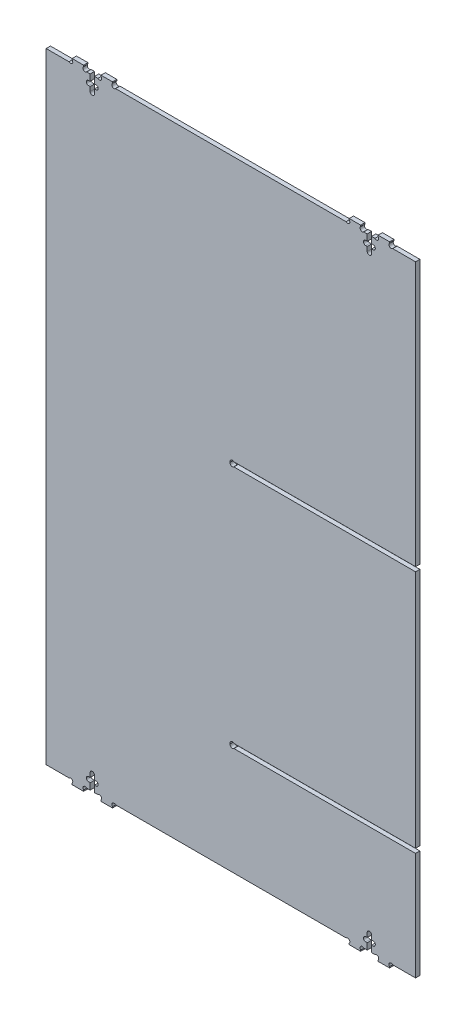
SolidWorks part; units mm, degrees
ref_plane "Спереди" through (0, 0, 0) normal (0, 0, 1) x (1, 0, 0)
ref_plane "Сверху" through (0, 0, 0) normal (0, 1, 0) x (1, 0, 0)
ref_plane "Справа" through (0, 0, 0) normal (1, 0, 0) x (0, 0, -1)
sketch "Эскиз1" plane through (0, 0, 0) normal (0, 0, 1) x (1, 0, 0)
  line L1 (171.206, 664.8747) -> (-352.794, 664.8747)
  line L2 (171.206, 664.8747) -> (171.206, -200.7253)
  line L3 (171.206, -200.7253) -> (-352.794, -200.7253)
  line L4 (-352.794, 664.8747) -> (-352.794, -200.7253)
  dimension "X001" = 352.794
  dimension "X002" = 171.206
  dimension "Y001" = 200.7253
  dimension "Y002" = 664.8747
extrude "Бобышка-Вытянуть1" add sketch "Эскиз1" against normal blind 6
sketch "Стыки_эскиз_добавленных_шипов" plane through (0, 0, 0) normal (0, 0, 1) x (1, 0, 0)
  line L0 (-254.794, -206.7253) -> (-254.794, -200.7153)
  line L1 (-254.794, -200.7153) -> (-270.794, -200.7153)
  line L2 (-270.794, -200.7153) -> (-270.794, -206.7253)
  line L3 (-270.794, -206.7253) -> (-254.794, -206.7253)
  line L4 (-294.794, -200.7153) -> (-310.794, -200.7153)
  line L5 (-310.794, -200.7153) -> (-310.794, -206.7253)
  line L6 (-310.794, -206.7253) -> (-294.794, -206.7253)
  line L7 (-294.794, -206.7253) -> (-294.794, -200.7153)
  line L8 (129.206, -200.7153) -> (113.206, -200.7153)
  line L9 (113.206, -200.7153) -> (113.206, -206.7253)
  line L10 (113.206, -206.7253) -> (129.206, -206.7253)
  line L11 (129.206, -206.7253) -> (129.206, -200.7153)
  line L12 (73.206, -206.7253) -> (89.206, -206.7253)
  line L13 (89.206, -206.7253) -> (89.206, -200.7153)
  line L14 (89.206, -200.7153) -> (73.206, -200.7153)
  line L15 (73.206, -200.7153) -> (73.206, -206.7253)
  dimension "X001" = 310.794
  dimension "X002" = 294.794
  dimension "X003" = 270.794
  dimension "X004" = 254.794
  dimension "X005" = 73.206
  dimension "X006" = 89.206
  dimension "X007" = 113.206
  dimension "X008" = 129.206
  dimension "Y001" = 206.7253
  dimension "Y002" = 200.7153
extrude "Стыки_добавленные_шипы_6мм" add sketch "Стыки_эскиз_добавленных_шипов" against normal blind 6
sketch "Стыки_эскиз_пазов_и_стяжек_М5" plane through (0, 0, 0) normal (0, 0, 1) x (1, 0, 0)
  line L0 (-280.044, -190.8753) -> (-278.644, -190.8753)
  line L1 (-278.644, -190.8753) -> (-278.644, -186.5753)
  line L2 (-278.644, -186.5753) -> (-280.044, -186.5753)
  line L3 (-280.044, -186.5753) -> (-280.044, -179.7253)
  line L4 (-280.044, -179.7253) -> (-285.544, -179.7253)
  line L5 (-285.544, -179.7253) -> (-285.544, -186.5753)
  line L6 (-285.544, -186.5753) -> (-286.944, -186.5753)
  line L7 (-286.944, -186.5753) -> (-286.944, -190.8753)
  line L8 (-286.944, -190.8753) -> (-285.544, -190.8753)
  line L9 (-285.544, -190.8753) -> (-285.544, -206.8253)
  line L10 (-285.544, -206.8253) -> (-280.044, -206.8253)
  line L11 (-280.044, -206.8253) -> (-280.044, -190.8753)
  line L12 (-352.894, 664.8747) -> (-352.894, 658.8747)
  line L13 (-352.894, 658.8747) -> (-352.794, 658.8747)
  line L14 (-352.794, 658.8747) -> (-352.794, -200.7253)
  line L15 (-352.794, -200.7253) -> (-346.794, -200.7253)
  line L16 (-346.794, -200.7253) -> (-346.794, 658.8747)
  line L17 (-346.794, 658.8747) -> (-310.794, 658.8747)
  line L18 (-310.794, 658.8747) -> (-310.794, 664.8747)
  line L19 (-310.794, 664.8747) -> (-352.894, 664.8747)
  line L20 (-90.869, -51.2003) -> (165.206, -51.2003)
  line L21 (165.206, -51.2003) -> (165.206, -200.7253)
  line L22 (165.206, -200.7253) -> (171.206, -200.7253)
  line L23 (171.206, -200.7253) -> (171.206, -51.2003)
  line L24 (171.206, -51.2003) -> (171.306, -51.2003)
  line L25 (171.306, -51.2003) -> (171.306, -45.0503)
  line L26 (171.306, -45.0503) -> (171.206, -45.0503)
  line L27 (171.206, -45.0503) -> (171.206, 286.7997)
  line L28 (171.206, 286.7997) -> (171.306, 286.7997)
  line L29 (171.306, 286.7997) -> (171.306, 292.9497)
  line L30 (171.306, 292.9497) -> (171.206, 292.9497)
  line L31 (171.206, 292.9497) -> (171.206, 658.8747)
  line L32 (171.206, 658.8747) -> (171.306, 658.8747)
  line L33 (171.306, 658.8747) -> (171.306, 664.8747)
  line L34 (171.306, 664.8747) -> (129.206, 664.8747)
  line L35 (129.206, 664.8747) -> (129.206, 658.8747)
  line L36 (129.206, 658.8747) -> (165.206, 658.8747)
  line L37 (165.206, 658.8747) -> (165.206, 292.9497)
  line L38 (165.206, 292.9497) -> (-90.869, 292.9497)
  line L39 (-90.869, 292.9497) -> (-90.869, 286.7997)
  line L40 (-90.869, 286.7997) -> (165.206, 286.7997)
  line L41 (165.206, 286.7997) -> (165.206, -45.0503)
  line L42 (165.206, -45.0503) -> (-90.869, -45.0503)
  line L43 (-90.869, -45.0503) -> (-90.869, -51.2003)
  line L44 (98.456, 658.8747) -> (98.456, 649.0247)
  line L45 (98.456, 649.0247) -> (97.056, 649.0247)
  line L46 (97.056, 649.0247) -> (97.056, 644.7247)
  line L47 (97.056, 644.7247) -> (98.456, 644.7247)
  line L48 (98.456, 644.7247) -> (98.456, 637.8747)
  line L49 (98.456, 637.8747) -> (103.956, 637.8747)
  line L50 (103.956, 637.8747) -> (103.956, 644.7247)
  line L51 (103.956, 644.7247) -> (105.356, 644.7247)
  line L52 (105.356, 644.7247) -> (105.356, 649.0247)
  line L53 (105.356, 649.0247) -> (103.956, 649.0247)
  line L54 (103.956, 649.0247) -> (103.956, 658.8747)
  line L55 (103.956, 658.8747) -> (113.206, 658.8747)
  line L56 (113.206, 658.8747) -> (113.206, 664.8747)
  line L57 (113.206, 664.8747) -> (103.956, 664.8747)
  line L58 (103.956, 664.8747) -> (103.956, 664.9747)
  line L59 (103.956, 664.9747) -> (98.456, 664.9747)
  line L60 (98.456, 664.9747) -> (98.456, 664.8747)
  line L61 (98.456, 664.8747) -> (89.206, 664.8747)
  line L62 (89.206, 664.8747) -> (89.206, 658.8747)
  line L63 (89.206, 658.8747) -> (98.456, 658.8747)
  line L64 (-285.544, 658.8747) -> (-285.544, 649.0247)
  line L65 (-285.544, 649.0247) -> (-286.944, 649.0247)
  line L66 (-286.944, 649.0247) -> (-286.944, 644.7247)
  line L67 (-286.944, 644.7247) -> (-285.544, 644.7247)
  line L68 (-285.544, 644.7247) -> (-285.544, 637.8747)
  line L69 (-285.544, 637.8747) -> (-280.044, 637.8747)
  line L70 (-280.044, 637.8747) -> (-280.044, 644.7247)
  line L71 (-280.044, 644.7247) -> (-278.644, 644.7247)
  line L72 (-278.644, 644.7247) -> (-278.644, 649.0247)
  line L73 (-278.644, 649.0247) -> (-280.044, 649.0247)
  line L74 (-280.044, 649.0247) -> (-280.044, 658.8747)
  line L75 (-280.044, 658.8747) -> (-270.794, 658.8747)
  line L76 (-270.794, 658.8747) -> (-270.794, 664.8747)
  line L77 (-270.794, 664.8747) -> (-280.044, 664.8747)
  line L78 (-280.044, 664.8747) -> (-280.044, 664.9747)
  line L79 (-280.044, 664.9747) -> (-285.544, 664.9747)
  line L80 (-285.544, 664.9747) -> (-285.544, 664.8747)
  line L81 (-285.544, 664.8747) -> (-294.794, 664.8747)
  line L82 (-294.794, 664.8747) -> (-294.794, 658.8747)
  line L83 (-294.794, 658.8747) -> (-285.544, 658.8747)
  line L84 (103.956, -206.8253) -> (103.956, -190.8753)
  line L85 (103.956, -190.8753) -> (105.356, -190.8753)
  line L86 (105.356, -190.8753) -> (105.356, -186.5753)
  line L87 (105.356, -186.5753) -> (103.956, -186.5753)
  line L88 (103.956, -186.5753) -> (103.956, -179.7253)
  line L89 (103.956, -179.7253) -> (98.456, -179.7253)
  line L90 (98.456, -179.7253) -> (98.456, -186.5753)
  line L91 (98.456, -186.5753) -> (97.056, -186.5753)
  line L92 (97.056, -186.5753) -> (97.056, -190.8753)
  line L93 (97.056, -190.8753) -> (98.456, -190.8753)
  line L94 (98.456, -190.8753) -> (98.456, -206.8253)
  line L95 (98.456, -206.8253) -> (103.956, -206.8253)
  line L96 (73.206, 658.8747) -> (73.206, 664.8747)
  line L97 (73.206, 664.8747) -> (-254.794, 664.8747)
  line L98 (-254.794, 664.8747) -> (-254.794, 658.8747)
  line L99 (-254.794, 658.8747) -> (73.206, 658.8747)
  dimension "X001" = 352.894
  dimension "X002" = 352.794
  dimension "X003" = 346.794
  dimension "X004" = 310.794
  dimension "X005" = 294.794
  dimension "X006" = 286.944
  dimension "X007" = 285.544
  dimension "X008" = 280.044
  dimension "X009" = 278.644
  dimension "X010" = 270.794
  dimension "X011" = 254.794
  dimension "X012" = 90.869
  dimension "X013" = 73.206
  dimension "X014" = 89.206
  dimension "X015" = 97.056
  dimension "X016" = 98.456
  dimension "X017" = 103.956
  dimension "X018" = 105.356
  dimension "X019" = 113.206
  dimension "X020" = 129.206
  dimension "X021" = 165.206
  dimension "X022" = 171.206
  dimension "X023" = 171.306
  dimension "Y001" = 206.8253
  dimension "Y002" = 200.7253
  dimension "Y003" = 190.8753
  dimension "Y004" = 186.5753
  dimension "Y005" = 179.7253
  dimension "Y006" = 51.2003
  dimension "Y007" = 45.0503
  dimension "Y008" = 286.7997
  dimension "Y009" = 292.9497
  dimension "Y010" = 637.8747
  dimension "Y011" = 644.7247
  dimension "Y012" = 649.0247
  dimension "Y013" = 658.8747
  dimension "Y014" = 664.8747
  dimension "Y015" = 664.9747
extrude "Стыки_шип_паз_стяжки_М5" cut sketch "Стыки_эскиз_пазов_и_стяжек_М5" against normal through all and the other way through all
sketch "ЧПУ_М6_01_Центр" plane through (0, 0, 0) normal (0, 0, 1) x (1, 0, 0)
  line L0 (-286.944, 644.7247) -> (-286.944, 649.0247) construction
  line L1 (-278.644, 644.7247) -> (-280.044, 644.7247) construction
  point P0 (-282.794, 646.8747)
  dimension "От_кромки_по_X" = 4.15
  dimension "От_кромки_по_Y" = 2.15
sketch "ЧПУ_М6_01_Канал_эскиз" plane through (0, 0, 0) normal (0, 0, 1) x (1, 0, 0)
  line L0 (-285.794, 637.7747) -> (-279.794, 637.7747)
  line L1 (-279.794, 637.7747) -> (-279.794, 658.9747)
  line L2 (-279.794, 658.9747) -> (-285.794, 658.9747)
  line L3 (-285.794, 658.9747) -> (-285.794, 637.7747)
  line L4 (-285.794, 637.7747) -> (-279.794, 658.9747) construction
  point P4 (-282.794, 648.3747)
  dimension "Ширина" = 6
  dimension "Глубина" = 21.2
  dimension "Положение_ОтКромки" = 1.5
extrude "ЧПУ_М6_01_Канал" cut sketch "ЧПУ_М6_01_Канал_эскиз" against normal through all and the other way through all
sketch "ЧПУ_М6_01_Гайка_эскиз" plane through (0, 0, 0) normal (0, 0, 1) x (1, 0, 0)
  line L0 (-287.944, 643.7747) -> (-277.644, 643.7747)
  line L1 (-277.644, 643.7747) -> (-277.644, 649.9747)
  line L2 (-277.644, 649.9747) -> (-287.944, 649.9747)
  line L3 (-287.944, 649.9747) -> (-287.944, 643.7747)
  line L4 (-287.944, 643.7747) -> (-277.644, 649.9747) construction
  point P4 (-282.794, 646.8747)
  dimension "Ширина" = 10.3
  dimension "Глубина" = 6.2
extrude "ЧПУ_М6_01_Гайка" cut sketch "ЧПУ_М6_01_Гайка_эскиз" against normal through all and the other way through all
sketch "ЧПУ_М6_01_Т_эскиз_1" plane through (0, 0, 0) normal (0, 0, 1) x (1, 0, 0)
  circle A0 centre (-277.644, 646.9247) radius 3.05
  circle A1 centre (-287.944, 646.9247) radius 3.05
  dimension "Диаметр1" = 6.1
  dimension "Диаметр2" = 6.1
  dimension "Центр1_ПоОси" = 5.15
  dimension "Центр1_ОтКромки" = 0.05
  dimension "Центр2_ПоОси" = 5.15
  dimension "Центр2_ОтКромки" = 0.05
extrude "ЧПУ_М6_01_Т_разгрузка_1" cut sketch "ЧПУ_М6_01_Т_эскиз_1" against normal through all and the other way through all
sketch "ЧПУ_М6_01_Т_эскиз_-1" plane through (0, 0, 0) normal (0, 0, 1) x (1, 0, 0)
  circle A0 centre (-277.644, 646.8247) radius 3.05
  circle A1 centre (-287.944, 646.8247) radius 3.05
  dimension "Диаметр1" = 6.1
  dimension "Диаметр2" = 6.1
  dimension "Центр1_ПоОси" = 5.15
  dimension "Центр1_ОтКромки" = 0.05
  dimension "Центр2_ПоОси" = 5.15
  dimension "Центр2_ОтКромки" = 0.05
extrude "ЧПУ_М6_01_Т_разгрузка_-1" cut sketch "ЧПУ_М6_01_Т_эскиз_-1" against normal through all and the other way through all
sketch "ЧПУ_М6_01_Конец_эскиз" plane through (0, 0, 0) normal (0, 0, 1) x (1, 0, 0)
  circle A0 centre (-282.794, 637.7747) radius 3
  dimension "Центр1_ОтКромки" = 9.1
extrude "ЧПУ_М6_01_Конец" cut sketch "ЧПУ_М6_01_Конец_эскиз" against normal through all and the other way through all
sketch "ЧПУ_М6_02_Центр" plane through (0, 0, 0) normal (0, 0, 1) x (1, 0, 0)
  line L0 (97.056, 644.7247) -> (97.056, 649.0247) construction
  line L1 (105.356, 644.7247) -> (103.956, 644.7247) construction
  point P0 (101.206, 646.8747)
  dimension "От_кромки_по_X" = 4.15
  dimension "От_кромки_по_Y" = 2.15
sketch "ЧПУ_М6_02_Канал_эскиз" plane through (0, 0, 0) normal (0, 0, 1) x (1, 0, 0)
  line L0 (98.206, 637.7747) -> (104.206, 637.7747)
  line L1 (104.206, 637.7747) -> (104.206, 658.9747)
  line L2 (104.206, 658.9747) -> (98.206, 658.9747)
  line L3 (98.206, 658.9747) -> (98.206, 637.7747)
  line L4 (98.206, 637.7747) -> (104.206, 658.9747) construction
  point P4 (101.206, 648.3747)
  dimension "Ширина" = 6
  dimension "Глубина" = 21.2
  dimension "Положение_ОтКромки" = 1.5
extrude "ЧПУ_М6_02_Канал" cut sketch "ЧПУ_М6_02_Канал_эскиз" against normal through all and the other way through all
sketch "ЧПУ_М6_02_Гайка_эскиз" plane through (0, 0, 0) normal (0, 0, 1) x (1, 0, 0)
  line L0 (96.056, 643.7747) -> (106.356, 643.7747)
  line L1 (106.356, 643.7747) -> (106.356, 649.9747)
  line L2 (106.356, 649.9747) -> (96.056, 649.9747)
  line L3 (96.056, 649.9747) -> (96.056, 643.7747)
  line L4 (96.056, 643.7747) -> (106.356, 649.9747) construction
  point P4 (101.206, 646.8747)
  dimension "Ширина" = 10.3
  dimension "Глубина" = 6.2
extrude "ЧПУ_М6_02_Гайка" cut sketch "ЧПУ_М6_02_Гайка_эскиз" against normal through all and the other way through all
sketch "ЧПУ_М6_02_Т_эскиз_1" plane through (0, 0, 0) normal (0, 0, 1) x (1, 0, 0)
  circle A0 centre (106.356, 646.9247) radius 3.05
  circle A1 centre (96.056, 646.9247) radius 3.05
  dimension "Диаметр1" = 6.1
  dimension "Диаметр2" = 6.1
  dimension "Центр1_ПоОси" = 5.15
  dimension "Центр1_ОтКромки" = 0.05
  dimension "Центр2_ПоОси" = 5.15
  dimension "Центр2_ОтКромки" = 0.05
extrude "ЧПУ_М6_02_Т_разгрузка_1" cut sketch "ЧПУ_М6_02_Т_эскиз_1" against normal through all and the other way through all
sketch "ЧПУ_М6_02_Т_эскиз_-1" plane through (0, 0, 0) normal (0, 0, 1) x (1, 0, 0)
  circle A0 centre (106.356, 646.8247) radius 3.05
  circle A1 centre (96.056, 646.8247) radius 3.05
  dimension "Диаметр1" = 6.1
  dimension "Диаметр2" = 6.1
  dimension "Центр1_ПоОси" = 5.15
  dimension "Центр1_ОтКромки" = 0.05
  dimension "Центр2_ПоОси" = 5.15
  dimension "Центр2_ОтКромки" = 0.05
extrude "ЧПУ_М6_02_Т_разгрузка_-1" cut sketch "ЧПУ_М6_02_Т_эскиз_-1" against normal through all and the other way through all
sketch "ЧПУ_М6_02_Конец_эскиз" plane through (0, 0, 0) normal (0, 0, 1) x (1, 0, 0)
  circle A0 centre (101.206, 637.7747) radius 3
  dimension "Центр1_ОтКромки" = 9.1
extrude "ЧПУ_М6_02_Конец" cut sketch "ЧПУ_М6_02_Конец_эскиз" against normal through all and the other way through all
sketch "ЧПУ_М6_03_Центр" plane through (0, 0, 0) normal (0, 0, 1) x (1, 0, 0)
  line L0 (97.056, -190.8753) -> (97.056, -186.5753) construction
  line L1 (105.356, -190.8753) -> (103.956, -190.8753) construction
  point P0 (101.206, -188.7253)
  dimension "От_кромки_по_X" = 4.15
  dimension "От_кромки_по_Y" = 2.15
sketch "ЧПУ_М6_03_Канал_эскиз" plane through (0, 0, 0) normal (0, 0, 1) x (1, 0, 0)
  line L0 (98.206, -200.8253) -> (104.206, -200.8253)
  line L1 (104.206, -200.8253) -> (104.206, -179.6253)
  line L2 (104.206, -179.6253) -> (98.206, -179.6253)
  line L3 (98.206, -179.6253) -> (98.206, -200.8253)
  line L4 (98.206, -200.8253) -> (104.206, -179.6253) construction
  point P4 (101.206, -190.2253)
  dimension "Ширина" = 6
  dimension "Глубина" = 21.2
  dimension "Положение_ОтКромки" = 1.5
extrude "ЧПУ_М6_03_Канал" cut sketch "ЧПУ_М6_03_Канал_эскиз" against normal through all and the other way through all
sketch "ЧПУ_М6_03_Гайка_эскиз" plane through (0, 0, 0) normal (0, 0, 1) x (1, 0, 0)
  line L0 (96.056, -191.8253) -> (106.356, -191.8253)
  line L1 (106.356, -191.8253) -> (106.356, -185.6253)
  line L2 (106.356, -185.6253) -> (96.056, -185.6253)
  line L3 (96.056, -185.6253) -> (96.056, -191.8253)
  line L4 (96.056, -191.8253) -> (106.356, -185.6253) construction
  point P4 (101.206, -188.7253)
  dimension "Ширина" = 10.3
  dimension "Глубина" = 6.2
extrude "ЧПУ_М6_03_Гайка" cut sketch "ЧПУ_М6_03_Гайка_эскиз" against normal through all and the other way through all
sketch "ЧПУ_М6_03_Т_эскиз_1" plane through (0, 0, 0) normal (0, 0, 1) x (1, 0, 0)
  circle A0 centre (106.356, -188.6753) radius 3.05
  circle A1 centre (96.056, -188.6753) radius 3.05
  dimension "Диаметр1" = 6.1
  dimension "Диаметр2" = 6.1
  dimension "Центр1_ПоОси" = 5.15
  dimension "Центр1_ОтКромки" = 0.05
  dimension "Центр2_ПоОси" = 5.15
  dimension "Центр2_ОтКромки" = 0.05
extrude "ЧПУ_М6_03_Т_разгрузка_1" cut sketch "ЧПУ_М6_03_Т_эскиз_1" against normal through all and the other way through all
sketch "ЧПУ_М6_03_Т_эскиз_-1" plane through (0, 0, 0) normal (0, 0, 1) x (1, 0, 0)
  circle A0 centre (106.356, -188.7753) radius 3.05
  circle A1 centre (96.056, -188.7753) radius 3.05
  dimension "Диаметр1" = 6.1
  dimension "Диаметр2" = 6.1
  dimension "Центр1_ПоОси" = 5.15
  dimension "Центр1_ОтКромки" = 0.05
  dimension "Центр2_ПоОси" = 5.15
  dimension "Центр2_ОтКромки" = 0.05
extrude "ЧПУ_М6_03_Т_разгрузка_-1" cut sketch "ЧПУ_М6_03_Т_эскиз_-1" against normal through all and the other way through all
sketch "ЧПУ_М6_03_Конец_эскиз" plane through (0, 0, 0) normal (0, 0, 1) x (1, 0, 0)
  circle A0 centre (101.206, -179.6253) radius 3
  dimension "Центр1_ОтКромки" = 9.1
extrude "ЧПУ_М6_03_Конец" cut sketch "ЧПУ_М6_03_Конец_эскиз" against normal through all and the other way through all
sketch "ЧПУ_М6_04_Центр" plane through (0, 0, 0) normal (0, 0, 1) x (1, 0, 0)
  line L0 (-286.944, -190.8753) -> (-286.944, -186.5753) construction
  line L1 (-278.644, -190.8753) -> (-280.044, -190.8753) construction
  point P0 (-282.794, -188.7253)
  dimension "От_кромки_по_X" = 4.15
  dimension "От_кромки_по_Y" = 2.15
sketch "ЧПУ_М6_04_Канал_эскиз" plane through (0, 0, 0) normal (0, 0, 1) x (1, 0, 0)
  line L0 (-285.794, -200.8253) -> (-279.794, -200.8253)
  line L1 (-279.794, -200.8253) -> (-279.794, -179.6253)
  line L2 (-279.794, -179.6253) -> (-285.794, -179.6253)
  line L3 (-285.794, -179.6253) -> (-285.794, -200.8253)
  line L4 (-285.794, -200.8253) -> (-279.794, -179.6253) construction
  point P4 (-282.794, -190.2253)
  dimension "Ширина" = 6
  dimension "Глубина" = 21.2
  dimension "Положение_ОтКромки" = 1.5
extrude "ЧПУ_М6_04_Канал" cut sketch "ЧПУ_М6_04_Канал_эскиз" against normal through all and the other way through all
sketch "ЧПУ_М6_04_Гайка_эскиз" plane through (0, 0, 0) normal (0, 0, 1) x (1, 0, 0)
  line L0 (-287.944, -191.8253) -> (-277.644, -191.8253)
  line L1 (-277.644, -191.8253) -> (-277.644, -185.6253)
  line L2 (-277.644, -185.6253) -> (-287.944, -185.6253)
  line L3 (-287.944, -185.6253) -> (-287.944, -191.8253)
  line L4 (-287.944, -191.8253) -> (-277.644, -185.6253) construction
  point P4 (-282.794, -188.7253)
  dimension "Ширина" = 10.3
  dimension "Глубина" = 6.2
extrude "ЧПУ_М6_04_Гайка" cut sketch "ЧПУ_М6_04_Гайка_эскиз" against normal through all and the other way through all
sketch "ЧПУ_М6_04_Т_эскиз_1" plane through (0, 0, 0) normal (0, 0, 1) x (1, 0, 0)
  circle A0 centre (-277.644, -188.6753) radius 3.05
  circle A1 centre (-287.944, -188.6753) radius 3.05
  dimension "Диаметр1" = 6.1
  dimension "Диаметр2" = 6.1
  dimension "Центр1_ПоОси" = 5.15
  dimension "Центр1_ОтКромки" = 0.05
  dimension "Центр2_ПоОси" = 5.15
  dimension "Центр2_ОтКромки" = 0.05
extrude "ЧПУ_М6_04_Т_разгрузка_1" cut sketch "ЧПУ_М6_04_Т_эскиз_1" against normal through all and the other way through all
sketch "ЧПУ_М6_04_Т_эскиз_-1" plane through (0, 0, 0) normal (0, 0, 1) x (1, 0, 0)
  circle A0 centre (-277.644, -188.7753) radius 3.05
  circle A1 centre (-287.944, -188.7753) radius 3.05
  dimension "Диаметр1" = 6.1
  dimension "Диаметр2" = 6.1
  dimension "Центр1_ПоОси" = 5.15
  dimension "Центр1_ОтКромки" = 0.05
  dimension "Центр2_ПоОси" = 5.15
  dimension "Центр2_ОтКромки" = 0.05
extrude "ЧПУ_М6_04_Т_разгрузка_-1" cut sketch "ЧПУ_М6_04_Т_эскиз_-1" against normal through all and the other way through all
sketch "ЧПУ_М6_04_Конец_эскиз" plane through (0, 0, 0) normal (0, 0, 1) x (1, 0, 0)
  circle A0 centre (-282.794, -179.6253) radius 3
  dimension "Центр1_ОтКромки" = 9.1
extrude "ЧПУ_М6_04_Конец" cut sketch "ЧПУ_М6_04_Конец_эскиз" against normal through all and the other way through all
sketch "ЧПУ_Шаблон_углов_01" plane through (0, 0, 0) normal (0, 0, 1) x (1, 0, 0)
  line L0 (-270.794, 664.8747) -> (-270.794, 658.8747) construction
  line L1 (-270.794, 658.8747) -> (-279.794, 658.8747) construction
  line L2 (73.206, 664.8747) -> (73.206, 658.8747) construction
  line L3 (73.206, 658.8747) -> (-254.794, 658.8747) construction
  line L4 (113.206, 664.8747) -> (113.206, 658.8747) construction
  line L5 (113.206, 658.8747) -> (104.206, 658.8747) construction
  line L6 (-310.794, 664.8747) -> (-310.794, 658.8747) construction
  line L7 (-310.794, 658.8747) -> (-346.794, 658.8747) construction
  circle A0 centre (-272.9153, 660.996) radius 3.05
  circle A1 centre (71.0847, 660.996) radius 3.05
  circle A2 centre (111.0847, 660.996) radius 3.05
  circle A3 centre (-312.9153, 660.996) radius 3.05
  dimension "D3" = 6.1
  dimension "D6" = 6.1
  dimension "D9" = 6.1
  dimension "D12" = 6.1
  dimension "D1" = 2.1213
  dimension "D2" = 2.1213
  dimension "D4" = 2.1213
  dimension "D5" = 2.1213
  dimension "D7" = 2.1213
  dimension "D8" = 2.1213
  dimension "D10" = 2.1213
  dimension "D11" = 2.1213
sketch "ЧПУ_Шаблон_углов_02" plane through (0, 0, 0) normal (0, 0, 1) x (1, 0, 0)
  line L0 (-254.794, 658.8747) -> (-254.794, 664.8747) construction
  line L1 (73.206, 658.8747) -> (-254.794, 658.8747) construction
  line L2 (89.206, 658.8747) -> (89.206, 664.8747) construction
  line L3 (98.206, 658.8747) -> (89.206, 658.8747) construction
  line L4 (129.206, 658.8747) -> (129.206, 664.8747) construction
  line L5 (165.206, 658.8747) -> (129.206, 658.8747) construction
  line L6 (-90.869, 286.7997) -> (-90.869, 292.9497) construction
  line L7 (165.206, 286.7997) -> (-90.869, 286.7997) construction
  line L8 (-90.869, -51.2003) -> (-90.869, -45.0503) construction
  line L9 (165.206, -51.2003) -> (-90.869, -51.2003) construction
  line L10 (-294.794, 658.8747) -> (-294.794, 664.8747) construction
  line L11 (-285.794, 658.8747) -> (-294.794, 658.8747) construction
  circle A0 centre (-252.6727, 660.996) radius 3.05
  circle A1 centre (91.3273, 660.996) radius 3.05
  circle A2 centre (131.3273, 660.996) radius 3.05
  circle A3 centre (-88.7477, 288.921) radius 3.05
  circle A4 centre (-88.7477, -49.079) radius 3.05
  circle A5 centre (-292.6727, 660.996) radius 3.05
  dimension "D3" = 6.1
  dimension "D6" = 6.1
  dimension "D9" = 6.1
  dimension "D12" = 6.1
  dimension "D1" = 2.1213
  dimension "D2" = 2.1213
  dimension "D4" = 2.1213
  dimension "D5" = 2.1213
  dimension "D7" = 2.1213
  dimension "D8" = 2.1213
  dimension "D10" = 2.1213
  dimension "D11" = 2.1213
  dimension "D15" = 6.1
  dimension "D18" = 6.1
  dimension "D13" = 2.1213
  dimension "D14" = 2.1213
  dimension "D16" = 2.1213
  dimension "D17" = 2.1213
sketch "ЧПУ_Шаблон_углов_03" plane through (0, 0, 0) normal (0, 0, 1) x (1, 0, 0)
  line L0 (-90.869, 286.7997) -> (-90.869, 292.9497) construction
  line L1 (-90.869, 292.9497) -> (165.206, 292.9497) construction
  line L2 (-90.869, -51.2003) -> (-90.869, -45.0503) construction
  line L3 (-90.869, -45.0503) -> (165.206, -45.0503) construction
  line L4 (129.206, -206.7253) -> (129.206, -200.7253) construction
  line L5 (129.206, -200.7253) -> (165.206, -200.7253) construction
  line L6 (89.206, -206.7253) -> (89.206, -200.7253) construction
  line L7 (89.206, -200.7253) -> (98.206, -200.7253) construction
  line L8 (-254.794, -206.7253) -> (-254.794, -200.7253) construction
  line L9 (-254.794, -200.7253) -> (73.206, -200.7253) construction
  line L10 (-294.794, -206.7253) -> (-294.794, -200.7253) construction
  line L11 (-294.794, -200.7253) -> (-285.794, -200.7253) construction
  circle A0 centre (-88.7477, 290.8284) radius 3.05
  circle A1 centre (-88.7477, -47.1716) radius 3.05
  circle A2 centre (131.3273, -202.8466) radius 3.05
  circle A3 centre (91.3273, -202.8466) radius 3.05
  circle A4 centre (-252.6727, -202.8466) radius 3.05
  circle A5 centre (-292.6727, -202.8466) radius 3.05
  dimension "D3" = 6.1
  dimension "D6" = 6.1
  dimension "D9" = 6.1
  dimension "D12" = 6.1
  dimension "D1" = 2.1213
  dimension "D2" = 2.1213
  dimension "D4" = 2.1213
  dimension "D5" = 2.1213
  dimension "D7" = 2.1213
  dimension "D8" = 2.1213
  dimension "D10" = 2.1213
  dimension "D11" = 2.1213
  dimension "D15" = 6.1
  dimension "D18" = 6.1
  dimension "D13" = 2.1213
  dimension "D14" = 2.1213
  dimension "D16" = 2.1213
  dimension "D17" = 2.1213
sketch "ЧПУ_Шаблон_углов_04" plane through (0, 0, 0) normal (0, 0, 1) x (1, 0, 0)
  line L0 (113.206, -200.7253) -> (113.206, -206.7253) construction
  line L1 (104.206, -200.7253) -> (113.206, -200.7253) construction
  line L2 (73.206, -200.7253) -> (73.206, -206.7253) construction
  line L3 (-254.794, -200.7253) -> (73.206, -200.7253) construction
  line L4 (-270.794, -200.7253) -> (-270.794, -206.7253) construction
  line L5 (-279.794, -200.7253) -> (-270.794, -200.7253) construction
  line L6 (-310.794, -200.7253) -> (-310.794, -206.7253) construction
  line L7 (-346.794, -200.7253) -> (-310.794, -200.7253) construction
  circle A0 centre (111.0847, -202.8466) radius 3.05
  circle A1 centre (71.0847, -202.8466) radius 3.05
  circle A2 centre (-272.9153, -202.8466) radius 3.05
  circle A3 centre (-312.9153, -202.8466) radius 3.05
  dimension "D3" = 6.1
  dimension "D6" = 6.1
  dimension "D9" = 6.1
  dimension "D12" = 6.1
  dimension "D1" = 2.1213
  dimension "D2" = 2.1213
  dimension "D4" = 2.1213
  dimension "D5" = 2.1213
  dimension "D7" = 2.1213
  dimension "D8" = 2.1213
  dimension "D10" = 2.1213
  dimension "D11" = 2.1213
extrude "ЧПУ_Разгрузки_01" cut sketch "ЧПУ_Шаблон_углов_01" against normal through all and the other way through all
extrude "ЧПУ_Разгрузки_02" cut sketch "ЧПУ_Шаблон_углов_02" against normal through all and the other way through all
extrude "ЧПУ_Разгрузки_03" cut sketch "ЧПУ_Шаблон_углов_03" against normal through all and the other way through all
extrude "ЧПУ_Разгрузки_04" cut sketch "ЧПУ_Шаблон_углов_04" against normal through all and the other way through all
equation "\"Ширина груза\"= 420"
equation "\"Глубина груза\"= 490"
equation "\"Высота груза\"= 297"
equation "\"Ширина ячейки\"= \"Ширина груза\" + 10"
equation "\"Глубина ячейки\"= \"Глубина груза\" + 10"
equation "\"Высота ячейки\"= \"Высота груза\" + 10 + 13"
equation "\"Колво ячеек ширина\"= 2"
equation "\"Колво ячеек высота\"= 2"
equation "\"Толщина стенки\" = 6"
equation "\"Крепление дверцы\"= 5 "
equation "\"Ширина рейки\"= \"Толщина шестерни\""
equation "\"Высота рейки\"= 20"
equation "\"Высота пола\"= \"Толщина стенки\" * 2"
equation "\"Колво полозьев\"= 5"
equation "\"Отступ рейки\"= 20"
equation "\"Глубина каретки\"= \"Глубина ячейки\" + 30 + \"Мотор Y высота корпуса\" + 20"
equation "\"Длинна рейки\" = (\"Ширина ячейки\" + \"Толщина стенки\" + \"Крепление дверцы\") * \"Колво ячеек ширина\" + \"Ширина ячейки выгрузки\" * \"Колво выгрузки\" + \"Толщина стенки\" + \"Отступ крепления мотора фиксации\" * 2 - \"Крепление дверцы\" * \"Колво ячеек ширина\""
equation "\"Отступ шпильки\"= 26"
equation "\"Диаметр шпильки\"= 5"
equation "\"Длинна шпильки\"= ( \"Высота ячейки\" + \"Толщина стенки\" + \"Высота пола\" ) * \"Колво ячеек высота\" + ( \"Толщина стенки\" + \"Отступ рейки\" ) * 2 "
equation "\"Ширина пластины\"= 50  "
equation "\"Высота зона выгрузки\"= \"Высота ячейки\" * 2 + \"Толщина стенки\" * 2"
equation "\"Колво выгрузки\"= 1"
equation "\"Ширина ячейки выгрузки\"= \"Ширина ячейки\" + \"Толщина стенки\" + \"Отступ крепления мотора фиксации\"*2"
equation "\"Отступ крепления мотора фиксации\" = (\"Ширина пластины\" + 20 - \"Толщина стенки\") / 2"
equation "\"Мотор X ширина корпуса\"= 42.3"
equation "\"Мотор X высота корпуса\"= 42.3"
equation "\"Мотор X длина корпуса\"= 40"
equation "\"Мотор X вылет вала\"= 19.8"
equation "\"Мотор Y ширина корпуса\"= 42.3"
equation "\"Мотор Y высота корпуса\"= 42.3"
equation "\"Мотор Y длина корпуса\"= 48"
equation "\"Мотор Y вылет вала\"= 30"
equation "\"Мотор Z ширина корпуса\"= 42"
equation "\"Мотор Z высота корпуса\"= 42"
equation "\"Мотор Z длина корпуса\"= 40"
equation "\"Мотор Z вылет вала\"= 23"
equation "\"Мотор диаметр вала ПРЕДВ\"= 5"
equation "\"Мотор шаг крепления ПРЕДВ\"= 31"
equation "\"Мотор диаметр отверстий ПРЕДВ\"= 3"
equation "\"Мотор глубина отверстий ПРЕДВ\"= 4.5"
equation "\"Мотор диаметр буртика ПРЕДВ\"= 22"
equation "\"Мотор высота буртика ПРЕДВ\"= 2"
equation "\"Мотор диаметр шкива ПРЕДВ\"= 16"
equation "\"Мотор длина шкива ПРЕДВ\"= 12"
equation "\"Мотор отступ шкива ПРЕДВ\"= 5"
equation "\"Мотор X шаг градусов\"= 1.8"
equation "\"Мотор Y шаг градусов\"= 1.8"
equation "\"Мотор Z шаг градусов\"= 1.8"
equation "\"Мотор Y диаметр ротора\"= 25.78"
equation "\"Толщина шестерни\"= 10"
equation "\"D1@Бобышка-Вытянуть1\"=\"Толщина стенки\""
equation "\"Канал М6\"=6"
equation "\"Гайка под ключ\"=10.3"
equation "\"Длина кармана гайки\"=6.2"
equation "\"Основная фреза\"=6"
equation "\"Запас разгрузки\"=0.05"
equation "\"Ширина@ЧПУ_М6_01_Канал_эскиз\" = \"Канал М6\""
equation "\"Глубина@ЧПУ_М6_01_Канал_эскиз\" = 21.2"
equation "\"Положение_ОтКромки@ЧПУ_М6_01_Канал_эскиз\" = (1.5)"
equation "\"Ширина@ЧПУ_М6_01_Гайка_эскиз\" = \"Гайка под ключ\""
equation "\"Глубина@ЧПУ_М6_01_Гайка_эскиз\" = \"Длина кармана гайки\""
equation "\"Центр1_ПоОси@ЧПУ_М6_01_Т_эскиз_1\" = (\"Гайка под ключ\"/2)"
equation "\"Центр1_ОтКромки@ЧПУ_М6_01_Т_эскиз_1\" = (0.05)"
equation "\"Диаметр1@ЧПУ_М6_01_Т_эскиз_1\" = \"Основная фреза\"+2*\"Запас разгрузки\""
equation "\"Центр2_ПоОси@ЧПУ_М6_01_Т_эскиз_1\" = - (-\"Гайка под ключ\"/2)"
equation "\"Центр2_ОтКромки@ЧПУ_М6_01_Т_эскиз_1\" = (0.05)"
equation "\"Диаметр2@ЧПУ_М6_01_Т_эскиз_1\" = \"Основная фреза\"+2*\"Запас разгрузки\""
equation "\"Центр1_ПоОси@ЧПУ_М6_01_Т_эскиз_-1\" = (\"Гайка под ключ\"/2)"
equation "\"Центр1_ОтКромки@ЧПУ_М6_01_Т_эскиз_-1\" = - (-0.05)"
equation "\"Диаметр1@ЧПУ_М6_01_Т_эскиз_-1\" = \"Основная фреза\"+2*\"Запас разгрузки\""
equation "\"Центр2_ПоОси@ЧПУ_М6_01_Т_эскиз_-1\" = - (-\"Гайка под ключ\"/2)"
equation "\"Центр2_ОтКромки@ЧПУ_М6_01_Т_эскиз_-1\" = - (-0.05)"
equation "\"Диаметр2@ЧПУ_М6_01_Т_эскиз_-1\" = \"Основная фреза\"+2*\"Запас разгрузки\""
equation "\"Центр1_ОтКромки@ЧПУ_М6_01_Конец_эскиз\" = - (-9.1)"
equation "\"Диаметр1@ЧПУ_М6_01_Конец_эскиз\" = \"Канал М6\""
equation "\"Ширина@ЧПУ_М6_02_Канал_эскиз\" = \"Канал М6\""
equation "\"Глубина@ЧПУ_М6_02_Канал_эскиз\" = 21.2"
equation "\"Положение_ОтКромки@ЧПУ_М6_02_Канал_эскиз\" = (1.5)"
equation "\"Ширина@ЧПУ_М6_02_Гайка_эскиз\" = \"Гайка под ключ\""
equation "\"Глубина@ЧПУ_М6_02_Гайка_эскиз\" = \"Длина кармана гайки\""
equation "\"Центр1_ПоОси@ЧПУ_М6_02_Т_эскиз_1\" = (\"Гайка под ключ\"/2)"
equation "\"Центр1_ОтКромки@ЧПУ_М6_02_Т_эскиз_1\" = (0.05)"
equation "\"Диаметр1@ЧПУ_М6_02_Т_эскиз_1\" = \"Основная фреза\"+2*\"Запас разгрузки\""
equation "\"Центр2_ПоОси@ЧПУ_М6_02_Т_эскиз_1\" = - (-\"Гайка под ключ\"/2)"
equation "\"Центр2_ОтКромки@ЧПУ_М6_02_Т_эскиз_1\" = (0.05)"
equation "\"Диаметр2@ЧПУ_М6_02_Т_эскиз_1\" = \"Основная фреза\"+2*\"Запас разгрузки\""
equation "\"Центр1_ПоОси@ЧПУ_М6_02_Т_эскиз_-1\" = (\"Гайка под ключ\"/2)"
equation "\"Центр1_ОтКромки@ЧПУ_М6_02_Т_эскиз_-1\" = - (-0.05)"
equation "\"Диаметр1@ЧПУ_М6_02_Т_эскиз_-1\" = \"Основная фреза\"+2*\"Запас разгрузки\""
equation "\"Центр2_ПоОси@ЧПУ_М6_02_Т_эскиз_-1\" = - (-\"Гайка под ключ\"/2)"
equation "\"Центр2_ОтКромки@ЧПУ_М6_02_Т_эскиз_-1\" = - (-0.05)"
equation "\"Диаметр2@ЧПУ_М6_02_Т_эскиз_-1\" = \"Основная фреза\"+2*\"Запас разгрузки\""
equation "\"Центр1_ОтКромки@ЧПУ_М6_02_Конец_эскиз\" = - (-9.1)"
equation "\"Диаметр1@ЧПУ_М6_02_Конец_эскиз\" = \"Канал М6\""
equation "\"Ширина@ЧПУ_М6_03_Канал_эскиз\" = \"Канал М6\""
equation "\"Глубина@ЧПУ_М6_03_Канал_эскиз\" = 21.2"
equation "\"Положение_ОтКромки@ЧПУ_М6_03_Канал_эскиз\" = - (-1.5)"
equation "\"Ширина@ЧПУ_М6_03_Гайка_эскиз\" = \"Гайка под ключ\""
equation "\"Глубина@ЧПУ_М6_03_Гайка_эскиз\" = \"Длина кармана гайки\""
equation "\"Центр1_ПоОси@ЧПУ_М6_03_Т_эскиз_1\" = (\"Гайка под ключ\"/2)"
equation "\"Центр1_ОтКромки@ЧПУ_М6_03_Т_эскиз_1\" = (0.05)"
equation "\"Диаметр1@ЧПУ_М6_03_Т_эскиз_1\" = \"Основная фреза\"+2*\"Запас разгрузки\""
equation "\"Центр2_ПоОси@ЧПУ_М6_03_Т_эскиз_1\" = - (-\"Гайка под ключ\"/2)"
equation "\"Центр2_ОтКромки@ЧПУ_М6_03_Т_эскиз_1\" = (0.05)"
equation "\"Диаметр2@ЧПУ_М6_03_Т_эскиз_1\" = \"Основная фреза\"+2*\"Запас разгрузки\""
equation "\"Центр1_ПоОси@ЧПУ_М6_03_Т_эскиз_-1\" = (\"Гайка под ключ\"/2)"
equation "\"Центр1_ОтКромки@ЧПУ_М6_03_Т_эскиз_-1\" = - (-0.05)"
equation "\"Диаметр1@ЧПУ_М6_03_Т_эскиз_-1\" = \"Основная фреза\"+2*\"Запас разгрузки\""
equation "\"Центр2_ПоОси@ЧПУ_М6_03_Т_эскиз_-1\" = - (-\"Гайка под ключ\"/2)"
equation "\"Центр2_ОтКромки@ЧПУ_М6_03_Т_эскиз_-1\" = - (-0.05)"
equation "\"Диаметр2@ЧПУ_М6_03_Т_эскиз_-1\" = \"Основная фреза\"+2*\"Запас разгрузки\""
equation "\"Центр1_ОтКромки@ЧПУ_М6_03_Конец_эскиз\" = (9.1)"
equation "\"Диаметр1@ЧПУ_М6_03_Конец_эскиз\" = \"Канал М6\""
equation "\"Ширина@ЧПУ_М6_04_Канал_эскиз\" = \"Канал М6\""
equation "\"Глубина@ЧПУ_М6_04_Канал_эскиз\" = 21.2"
equation "\"Положение_ОтКромки@ЧПУ_М6_04_Канал_эскиз\" = - (-1.5)"
equation "\"Ширина@ЧПУ_М6_04_Гайка_эскиз\" = \"Гайка под ключ\""
equation "\"Глубина@ЧПУ_М6_04_Гайка_эскиз\" = \"Длина кармана гайки\""
equation "\"Центр1_ПоОси@ЧПУ_М6_04_Т_эскиз_1\" = (\"Гайка под ключ\"/2)"
equation "\"Центр1_ОтКромки@ЧПУ_М6_04_Т_эскиз_1\" = (0.05)"
equation "\"Диаметр1@ЧПУ_М6_04_Т_эскиз_1\" = \"Основная фреза\"+2*\"Запас разгрузки\""
equation "\"Центр2_ПоОси@ЧПУ_М6_04_Т_эскиз_1\" = - (-\"Гайка под ключ\"/2)"
equation "\"Центр2_ОтКромки@ЧПУ_М6_04_Т_эскиз_1\" = (0.05)"
equation "\"Диаметр2@ЧПУ_М6_04_Т_эскиз_1\" = \"Основная фреза\"+2*\"Запас разгрузки\""
equation "\"Центр1_ПоОси@ЧПУ_М6_04_Т_эскиз_-1\" = (\"Гайка под ключ\"/2)"
equation "\"Центр1_ОтКромки@ЧПУ_М6_04_Т_эскиз_-1\" = - (-0.05)"
equation "\"Диаметр1@ЧПУ_М6_04_Т_эскиз_-1\" = \"Основная фреза\"+2*\"Запас разгрузки\""
equation "\"Центр2_ПоОси@ЧПУ_М6_04_Т_эскиз_-1\" = - (-\"Гайка под ключ\"/2)"
equation "\"Центр2_ОтКромки@ЧПУ_М6_04_Т_эскиз_-1\" = - (-0.05)"
equation "\"Диаметр2@ЧПУ_М6_04_Т_эскиз_-1\" = \"Основная фреза\"+2*\"Запас разгрузки\""
equation "\"Центр1_ОтКромки@ЧПУ_М6_04_Конец_эскиз\" = (9.1)"
equation "\"Диаметр1@ЧПУ_М6_04_Конец_эскиз\" = \"Канал М6\""
equation "\"Фреза стыка\" = 6"
equation "\"Перебег разгрузки\" = 0.05"
equation "\"D1@ЧПУ_Шаблон_углов_01\" = \"Фреза стыка\"/(2*sqr(2))"
equation "\"D2@ЧПУ_Шаблон_углов_01\" = \"Фреза стыка\"/(2*sqr(2))"
equation "\"D3@ЧПУ_Шаблон_углов_01\" = \"Фреза стыка\"+2*\"Перебег разгрузки\""
equation "\"D4@ЧПУ_Шаблон_углов_01\" = \"Фреза стыка\"/(2*sqr(2))"
equation "\"D5@ЧПУ_Шаблон_углов_01\" = \"Фреза стыка\"/(2*sqr(2))"
equation "\"D6@ЧПУ_Шаблон_углов_01\" = \"Фреза стыка\"+2*\"Перебег разгрузки\""
equation "\"D7@ЧПУ_Шаблон_углов_01\" = \"Фреза стыка\"/(2*sqr(2))"
equation "\"D8@ЧПУ_Шаблон_углов_01\" = \"Фреза стыка\"/(2*sqr(2))"
equation "\"D9@ЧПУ_Шаблон_углов_01\" = \"Фреза стыка\"+2*\"Перебег разгрузки\""
equation "\"D10@ЧПУ_Шаблон_углов_01\" = \"Фреза стыка\"/(2*sqr(2))"
equation "\"D11@ЧПУ_Шаблон_углов_01\" = \"Фреза стыка\"/(2*sqr(2))"
equation "\"D12@ЧПУ_Шаблон_углов_01\" = \"Фреза стыка\"+2*\"Перебег разгрузки\""
equation "\"D1@ЧПУ_Шаблон_углов_02\" = \"Фреза стыка\"/(2*sqr(2))"
equation "\"D2@ЧПУ_Шаблон_углов_02\" = \"Фреза стыка\"/(2*sqr(2))"
equation "\"D3@ЧПУ_Шаблон_углов_02\" = \"Фреза стыка\"+2*\"Перебег разгрузки\""
equation "\"D4@ЧПУ_Шаблон_углов_02\" = \"Фреза стыка\"/(2*sqr(2))"
equation "\"D5@ЧПУ_Шаблон_углов_02\" = \"Фреза стыка\"/(2*sqr(2))"
equation "\"D6@ЧПУ_Шаблон_углов_02\" = \"Фреза стыка\"+2*\"Перебег разгрузки\""
equation "\"D7@ЧПУ_Шаблон_углов_02\" = \"Фреза стыка\"/(2*sqr(2))"
equation "\"D8@ЧПУ_Шаблон_углов_02\" = \"Фреза стыка\"/(2*sqr(2))"
equation "\"D9@ЧПУ_Шаблон_углов_02\" = \"Фреза стыка\"+2*\"Перебег разгрузки\""
equation "\"D10@ЧПУ_Шаблон_углов_02\" = \"Фреза стыка\"/(2*sqr(2))"
equation "\"D11@ЧПУ_Шаблон_углов_02\" = \"Фреза стыка\"/(2*sqr(2))"
equation "\"D12@ЧПУ_Шаблон_углов_02\" = \"Фреза стыка\"+2*\"Перебег разгрузки\""
equation "\"D13@ЧПУ_Шаблон_углов_02\" = \"Фреза стыка\"/(2*sqr(2))"
equation "\"D14@ЧПУ_Шаблон_углов_02\" = \"Фреза стыка\"/(2*sqr(2))"
equation "\"D15@ЧПУ_Шаблон_углов_02\" = \"Фреза стыка\"+2*\"Перебег разгрузки\""
equation "\"D16@ЧПУ_Шаблон_углов_02\" = \"Фреза стыка\"/(2*sqr(2))"
equation "\"D17@ЧПУ_Шаблон_углов_02\" = \"Фреза стыка\"/(2*sqr(2))"
equation "\"D18@ЧПУ_Шаблон_углов_02\" = \"Фреза стыка\"+2*\"Перебег разгрузки\""
equation "\"D1@ЧПУ_Шаблон_углов_03\" = \"Фреза стыка\"/(2*sqr(2))"
equation "\"D2@ЧПУ_Шаблон_углов_03\" = \"Фреза стыка\"/(2*sqr(2))"
equation "\"D3@ЧПУ_Шаблон_углов_03\" = \"Фреза стыка\"+2*\"Перебег разгрузки\""
equation "\"D4@ЧПУ_Шаблон_углов_03\" = \"Фреза стыка\"/(2*sqr(2))"
equation "\"D5@ЧПУ_Шаблон_углов_03\" = \"Фреза стыка\"/(2*sqr(2))"
equation "\"D6@ЧПУ_Шаблон_углов_03\" = \"Фреза стыка\"+2*\"Перебег разгрузки\""
equation "\"D7@ЧПУ_Шаблон_углов_03\" = \"Фреза стыка\"/(2*sqr(2))"
equation "\"D8@ЧПУ_Шаблон_углов_03\" = \"Фреза стыка\"/(2*sqr(2))"
equation "\"D9@ЧПУ_Шаблон_углов_03\" = \"Фреза стыка\"+2*\"Перебег разгрузки\""
equation "\"D10@ЧПУ_Шаблон_углов_03\" = \"Фреза стыка\"/(2*sqr(2))"
equation "\"D11@ЧПУ_Шаблон_углов_03\" = \"Фреза стыка\"/(2*sqr(2))"
equation "\"D12@ЧПУ_Шаблон_углов_03\" = \"Фреза стыка\"+2*\"Перебег разгрузки\""
equation "\"D13@ЧПУ_Шаблон_углов_03\" = \"Фреза стыка\"/(2*sqr(2))"
equation "\"D14@ЧПУ_Шаблон_углов_03\" = \"Фреза стыка\"/(2*sqr(2))"
equation "\"D15@ЧПУ_Шаблон_углов_03\" = \"Фреза стыка\"+2*\"Перебег разгрузки\""
equation "\"D16@ЧПУ_Шаблон_углов_03\" = \"Фреза стыка\"/(2*sqr(2))"
equation "\"D17@ЧПУ_Шаблон_углов_03\" = \"Фреза стыка\"/(2*sqr(2))"
equation "\"D18@ЧПУ_Шаблон_углов_03\" = \"Фреза стыка\"+2*\"Перебег разгрузки\""
equation "\"D1@ЧПУ_Шаблон_углов_04\" = \"Фреза стыка\"/(2*sqr(2))"
equation "\"D2@ЧПУ_Шаблон_углов_04\" = \"Фреза стыка\"/(2*sqr(2))"
equation "\"D3@ЧПУ_Шаблон_углов_04\" = \"Фреза стыка\"+2*\"Перебег разгрузки\""
equation "\"D4@ЧПУ_Шаблон_углов_04\" = \"Фреза стыка\"/(2*sqr(2))"
equation "\"D5@ЧПУ_Шаблон_углов_04\" = \"Фреза стыка\"/(2*sqr(2))"
equation "\"D6@ЧПУ_Шаблон_углов_04\" = \"Фреза стыка\"+2*\"Перебег разгрузки\""
equation "\"D7@ЧПУ_Шаблон_углов_04\" = \"Фреза стыка\"/(2*sqr(2))"
equation "\"D8@ЧПУ_Шаблон_углов_04\" = \"Фреза стыка\"/(2*sqr(2))"
equation "\"D9@ЧПУ_Шаблон_углов_04\" = \"Фреза стыка\"+2*\"Перебег разгрузки\""
equation "\"D10@ЧПУ_Шаблон_углов_04\" = \"Фреза стыка\"/(2*sqr(2))"
equation "\"D11@ЧПУ_Шаблон_углов_04\" = \"Фреза стыка\"/(2*sqr(2))"
equation "\"D12@ЧПУ_Шаблон_углов_04\" = \"Фреза стыка\"+2*\"Перебег разгрузки\""
